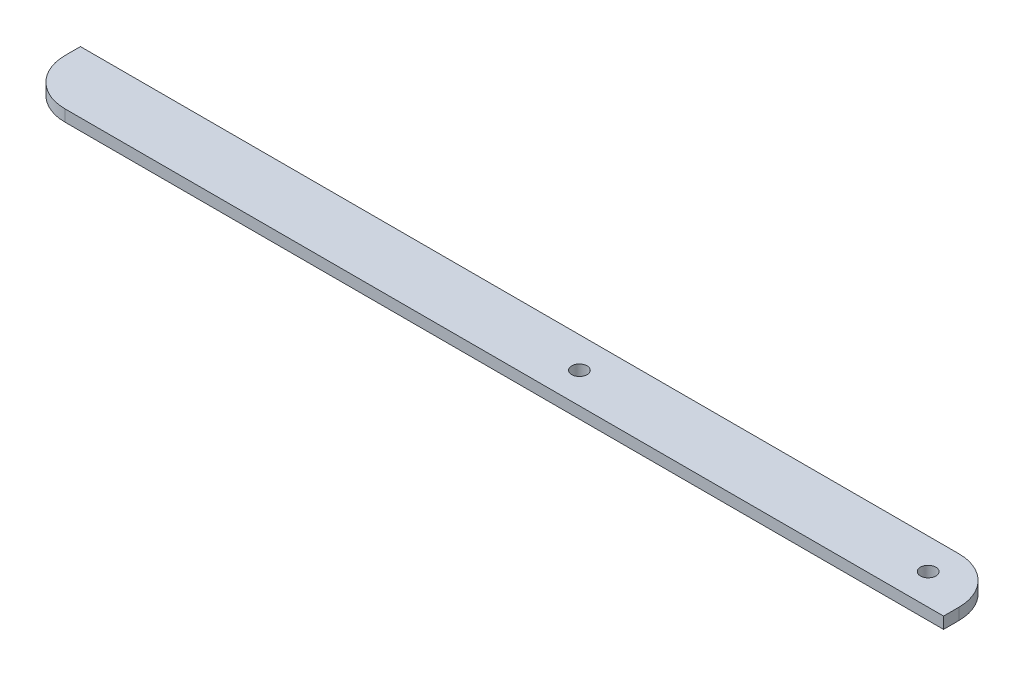
SolidWorks part; units mm, degrees
material "Pine"
ref_plane "Front Plane" through (0, 0, 0) normal (0, 0, 1) x (1, 0, 0)
ref_plane "Top Plane" through (0, 0, 0) normal (0, 1, 0) x (1, 0, 0)
ref_plane "Right Plane" through (0, 0, 0) normal (1, 0, 0) x (0, 0, -1)
sketch "Sketch1" plane through (0, 0, 0) normal (0, 1, 0) x (1, 0, 0)
  line L1 (-685.8, -50.8) -> (762, -50.8)
  line L2 (-762, 25.4) -> (-762, 50.8)
  line L3 (-762, 50.8) -> (685.8, 50.8)
  line L4 (762, -50.8) -> (762, -25.4)
  line L5 (-762, -50.8) -> (762, 50.8) construction
  line L6 (-762, 50.8) -> (762, -50.8) construction
  circle A0 centre (111.06, 0) radius 12.7
  circle A1 centre (685.8, 0) radius 12.7
  arc A2 (685.8, 50.8) -> (762, -25.4) centre (685.8, -25.4) cw
  arc A3 (-685.8, -50.8) -> (-762, 25.4) centre (-685.8, 25.4) cw
  point P0 (0, 0)
  dimension "D4" = 25.4
  dimension "D5" = 25.4
  dimension "D7" = 76.2
  dimension "D1" = 101.6
  dimension "D2" = 1524
  dimension "D3" = 574.74
  dimension "D6" = 76.2
extrude "Boss-Extrude1" add sketch "Sketch1" along normal blind 19.05
